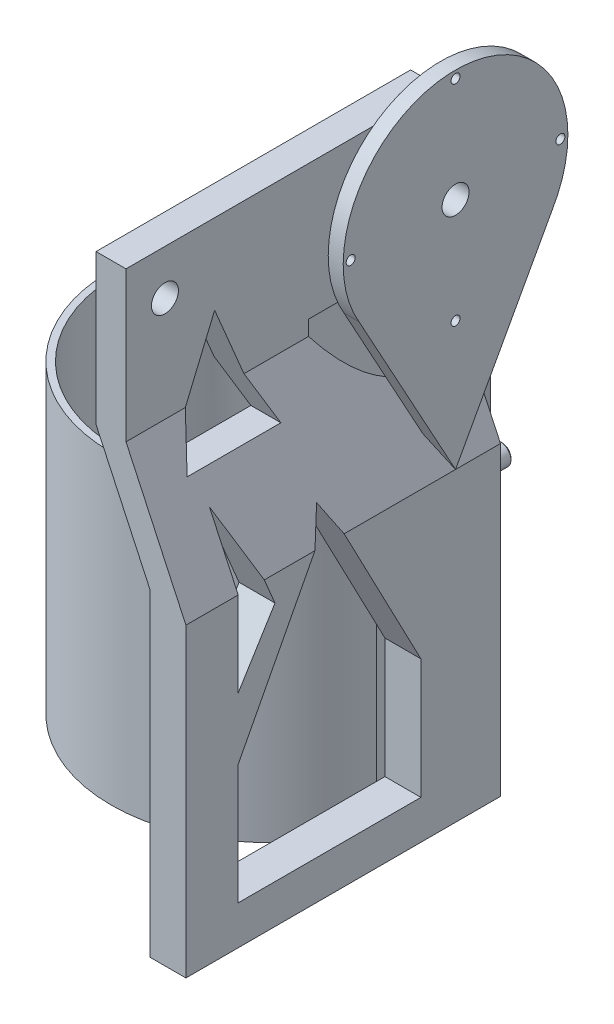
SolidWorks part; units mm, degrees
ref_plane "Front Plane" through (0, 0, 0) normal (0, 0, 1) x (1, 0, 0)
ref_plane "Top Plane" through (0, 0, 0) normal (0, 1, 0) x (1, 0, 0)
ref_plane "Right Plane" through (0, 0, 0) normal (1, 0, 0) x (0, 0, -1)
sketch "Sketch1" plane through (0, 0, 0) normal (0, 1, 0) x (1, 0, 0)
  circle A0 centre (0, 0) radius 52.5
  dimension "D1" = 105
extrude "Boss-Extrude1" add sketch "Sketch1" along normal blind 2
sketch "Sketch2" plane through (0, 2, 0) normal (0, 1, 0) x (1, 0, 0)
  circle A0 centre (0, 0) radius 52.5
  circle A1 centre (0, 0) radius 50.25
  circle A2 centre (0, 0) radius 52.5 construction
  dimension "D1" = 100.5
extrude "Boss-Extrude2" add sketch "Sketch2" along normal blind 100
sketch "Sketch5" plane through (68.8056, 0, 0) normal (1, 0, 0) x (0, 0, -1)
  line L0 (-10, 0) -> (5, 0) construction
  circle A0 centre (0, 180) radius 4.5
  circle A2 centre (-77, 180) radius 4.5
  dimension "D1" = 9
  dimension "D3" = 77
  dimension "D5" = 9
  dimension "D2" = 180
sketch "Sketch6" plane through (0, 0, 0) normal (0, 0, 1) x (1, 0, 0)
  line L0 (32.5, 195) -> (32.5, 145)
  line L1 (52.5, 0) -> (62.5, 0)
  line L2 (52.5, 0) -> (52.5, 102) construction
  line L4 (62.5, 0) -> (62.5, 102)
  line L6 (50.5, 106.3) -> (32.5, 145)
  line L8 (42.5, 195) -> (42.5, 145)
  line L9 (42.5, 145) -> (62.5, 102)
  line L10 (42.5, 195) -> (32.5, 195)
  line L11 (-52.5, 0) -> (52.5, 0) construction
  line L12 (52.5, 0) -> (52.5, 102) construction
  line L13 (50.5, 106.3) -> (50.5, 0)
  line L14 (52.5, 0) -> (50.5, 0)
  dimension "D1" = 102
  dimension "D2" = 10
  dimension "D3" = 2
  dimension "D5" = 20
  dimension "D6" = 10
extrude "Boss-Extrude3" add sketch "Sketch6" along normal blind 90 and the other way blind 15 separate body
sketch "Sketch7" plane through (42.5, 0, 0) normal (1, 0, 0) x (0, 0, -1)
  circle A0 centre (0, 180) radius 15
  dimension "D1" = 30
extrude "Boss-Extrude4" add sketch "Sketch7" along normal blind 15 and the other way blind 10
sketch "Sketch8" plane through (57.5, 0, 0) normal (1, 0, 0) x (0, 0, -1)
  circle A0 centre (0, 180) radius 37.5
  dimension "D1" = 75
extrude "Boss-Extrude5" add sketch "Sketch8" along normal blind 5
sketch "Sketch9" plane through (62.5, 0, 0) normal (1, 0, 0) x (0, 0, -1)
  circle A0 centre (-35, 180) radius 1.5
  circle A1 centre (0, 215) radius 1.5
  circle A2 centre (35, 180) radius 1.5
  circle A3 centre (0, 145) radius 1.5
  dimension "D2" = 3
  dimension "D3" = 3
  dimension "D5" = 3
  dimension "D6" = 3
  dimension "D1" = 35
  dimension "D4" = 35
  dimension "D7" = 35
  dimension "D8" = 35
extrude "Cut-Extrude1" cut sketch "Sketch9" against normal blind 6
extrude "Cut-Extrude2" cut sketch "Sketch5" against normal through all both and the other way through all
sketch "Sketch10" plane through (62.5, 0, 0) normal (1, 0, 0) x (0, 0, -1)
  line L0 (15, 0) -> (-90, 0) construction
  line L1 (7.5, 2) -> (-7.5, 2)
  line L2 (7.5, 2) -> (7.5, 6)
  line L4 (-7.5, 2) -> (-7.5, 6)
  arc A0 (-7.5, 6) -> (7.5, 6) centre (0, -0.8427) cw
  point P11 (0, 2)
  dimension "D1" = 2
  dimension "D2" = 4
  dimension "D3" = 15
extrude "Cut-Extrude3" cut sketch "Sketch10" against normal blind 20 from offset 4 offset against normal yes
sketch "Sketch11" plane through (0, 0, 0) normal (0, -1, 0) x (1, 0, 0)
  line L0 (50.5, 7.5) -> (58.5, 7.5) construction
  line L1 (52.5, 7.5) -> (60.5, 7.5)
  line L2 (52.5, 7.5) -> (52.5, -7.5)
  line L3 (52.5, -7.5) -> (60.5, -7.5)
  line L4 (60.5, 7.5) -> (60.5, -7.5)
  line L5 (62.5, -15) -> (62.5, 90) construction
  line L6 (50.5, -15) -> (50.5, 90) construction
  dimension "D1" = 2
  dimension "D2" = 2
  dimension "D3" = 15
extrude "Cut-Extrude4" cut sketch "Sketch11" against normal blind 95 from offset 3 offset against normal yes
sketch "Sketch12" plane through (0, 0, -15) normal (0, 0, -1) x (-1, 0, 0)
  line L1 (-52.5, 98) -> (-60.5, 98) construction
  line L2 (-60.5, 98) -> (-60.5, 3) construction
  circle A0 centre (-56.5, 93) radius 3
  dimension "D1" = 6
  dimension "D2" = 5
  dimension "D3" = 4
extrude "Cut-Extrude5" cut sketch "Sketch12" against normal blind 20
sketch "Sketch13" plane through (0, 0, -15) normal (0, 0, -1) x (-1, 0, 0)
  circle A0 centre (-56.5, 93) radius 3
  circle A1 centre (-56.5, 93) radius 3 construction
  circle A2 centre (-56.5, 93) radius 3.5
  dimension "D1" = 7
extrude "Boss-Extrude6" add sketch "Sketch13" along normal blind 6.5
chamfer "Chamfer1" distance 0.5 angle 45 1 edges at (53, 93, -21.5)
sketch "Sketch14" plane through (0, 102, 0) normal (0, 1, 0) x (1, 0, 0)
  circle A0 centre (0, 0) radius 51.5
  dimension "D1" = 103
extrude "Cut-Extrude6" cut sketch "Sketch14" along normal blind 48
sketch "Sketch15" plane through (62.5, 0, 0) normal (1, 0, 0) x (0, 0, -1)
  line L0 (-33.5128, 163.1731) -> (0, 102)
  line L1 (15, 102) -> (-90, 102) construction
  line L2 (0, 102) -> (33.5128, 163.1731)
  line L3 (33.5128, 163.1731) -> (-33.5128, 163.1731)
  circle A0 centre (0, 180) radius 37.5 construction
  circle A1 centre (0, 145) radius 1.5
extrude "Boss-Extrude7" add sketch "Sketch15" against normal up to surface (5 mm away) up to face at (57.5, 181.5, 35)
sketch "Sketch16" plane through (57.5, 0, 0) normal (-1, 0, 0) x (0, 0, 1)
  line L0 (-11.8572, 170.8127) -> (-3.8635, 104.9696)
  line L1 (-3.8635, 104.9696) -> (3.5428, 104.9696)
  line L2 (3.5428, 104.9696) -> (11.646, 170.5464)
  line L3 (-11.8572, 170.8127) -> (11.646, 170.5464)
  arc A0 (-15, 180) -> (0, 195) centre (0, 180) ccw construction
extrude "Boss-Extrude8" add sketch "Sketch16" along normal blind 5
sketch "Sketch17" plane through (0, 0, 0) normal (0, 0, 1) x (1, 0, 0)
  line L0 (44.979, 173.2476) -> (44.979, 165.8004)
  line L3 (44.979, 165.8004) -> (53.1619, 150.3087)
  line L5 (53.1619, 150.3087) -> (53.1619, 173.2476)
  line L6 (53.1619, 173.2476) -> (44.979, 173.2476)
extrude "Boss-Extrude9" add sketch "Sketch17" along normal blind 6 and the other way blind 6
sketch "Sketch18" plane through (0, 2, 0) normal (0, 1, 0) x (1, 0, 0)
  line L1 (35.0625, 11.4186) -> (39.4507, 11.4186)
  line L2 (35.0625, 11.4186) -> (35.0625, -27.9918)
  line L3 (35.0625, -27.9918) -> (39.4507, -27.9918)
  line L4 (39.4507, 11.4186) -> (39.4507, -27.9918)
  line L5 (35.2625, 11.2186) -> (39.2507, 11.2186)
  line L6 (35.2625, 11.2186) -> (35.2625, -27.7918)
  line L7 (35.2625, -27.7918) -> (39.2507, -27.7918)
  line L8 (39.2507, 11.2186) -> (39.2507, -27.7918)
  point P8 (37.2566, 11.2186)
  dimension "D1" = 0.2
  dimension "D2" = 0.2
  dimension "D3" = 0.2
  dimension "D4" = 0.2
extrude "Boss-Extrude10" add sketch "Sketch18" along normal up to surface (148 mm away) up to face at (37.5978, 150, 9.8491)
sketch "Sketch19" plane through (62.5, 0, 0) normal (1, 0, 0) x (0, 0, -1)
  line L0 (-72.5444, 13.0019) -> (-11.5673, 13.0019)
  line L1 (-11.5673, 13.0019) -> (-11.5673, 53.0553)
  line L2 (-11.5673, 53.0553) -> (-42.0558, 111.3101)
  line L3 (-42.0558, 111.3101) -> (-72.5444, 53.0553)
  line L4 (-72.5444, 53.0553) -> (-72.5444, 13.0019)
  line L5 (-76.0527, 131.1156) -> (-44.7701, 131.1156)
  line L6 (-44.7701, 131.1156) -> (-60.4114, 168.2454)
  line L7 (-60.4114, 168.2454) -> (-76.0527, 131.1156)
  line L8 (-72.5444, 73.6807) -> (-72.5444, 122.6672)
  line L9 (-72.5444, 122.6672) -> (-60.263, 93.5132)
  line L10 (-60.263, 93.5132) -> (-72.5444, 73.6807)
  point P6 (-42.0558, 13.0019)
extrude "Cut-Extrude7" cut sketch "Sketch19" against normal up to surface (12 mm away) up to face at (50.5, 69.4333, 38.1507)
extrude "Cut-Extrude8" cut sketch "Sketch19<2>" against normal up to surface (14.3303 mm away) up to face at (46.3253, 115.2756, 56.7405)
sketch "Sketch19<2>" plane through (62.5, 0, 0) normal (1, 0, 0) x (0, 0, -1) same geometry as "Sketch19"
